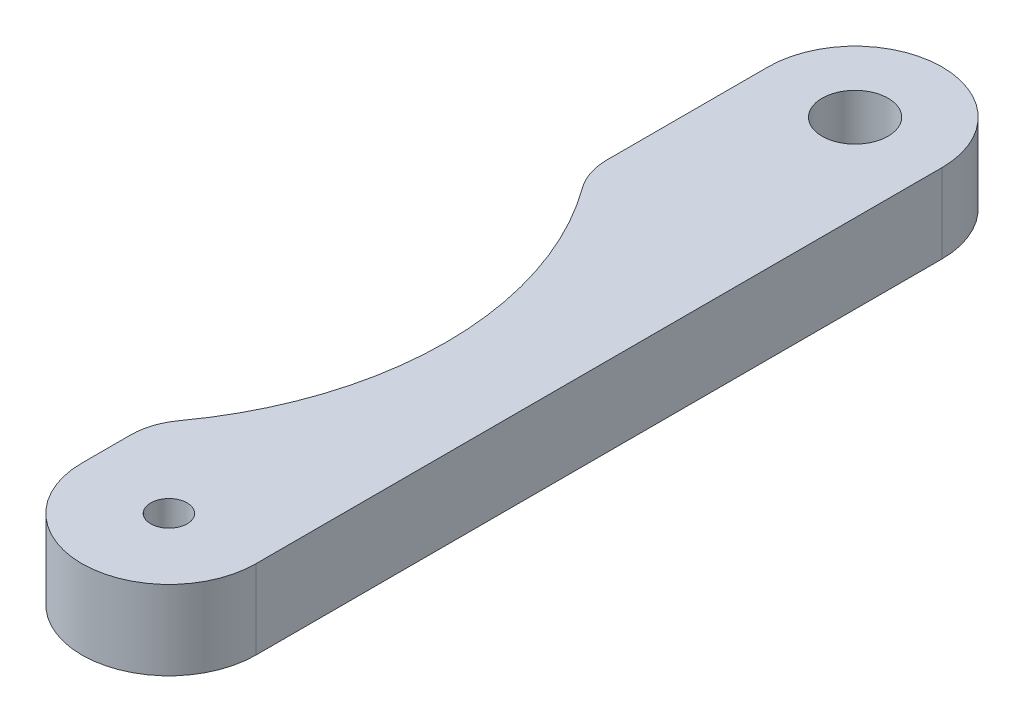
SolidWorks part; units mm, degrees
material "7075-T6, Plate (SS)"
ref_plane "Front Plane" through (0, 0, 0) normal (0, 0, 1) x (1, 0, 0)
ref_plane "Top Plane" through (0, 0, 0) normal (0, 1, 0) x (1, 0, 0)
ref_plane "Right Plane" through (0, 0, 0) normal (1, 0, 0) x (0, 0, -1)
sketch "Sketch1" plane through (0, 0, 0) normal (0, 1, 0) x (1, 0, 0)
  line L0 (0.3077, 6.5172) -> (0.3077, -26.5028)
  line L1 (8.6897, 6.5172) -> (8.6897, -26.5028)
  arc A0 (0.3077, 6.5172) -> (8.6897, 6.5172) centre (4.4987, 6.5172) cw
  arc A1 (8.6897, -26.5028) -> (0.3077, -26.5028) centre (4.4987, -26.5028) cw
  dimension "D1" = 33.02
  dimension "D2" = 8.382
extrude "Boss-Extrude1" add sketch "Sketch1" along normal blind 3.81
hole_wizard "#4-40 Tapped Hole1" positions "Sketch2" profile "Sketch3" tap size "#4-40" standard "ANSI Inch" end condition through all
sketch "Sketch2" plane through (0, 3.81, 0) normal (0, 1, 0) x (1, 0, 0)
  arc A0 (0.3077, -26.5028) -> (8.6897, -26.5028) centre (4.4987, -26.5028) ccw construction
  arc A1 (8.6897, 6.5172) -> (0.3077, 6.5172) centre (4.4987, 6.5172) ccw construction
  point P0 (4.4987, 6.5172)
  point P2 (4.4987, -26.5028)
sketch "Sketch3" plane through (4.4987, 3.81, -6.5172) normal (1, 0, 0) x (0, 0, 1)
  line L0 (0, 0) -> (0, 3.81)
  line L1 (0, 3.81) -> (0.8763, 3.81)
  line L2 (0.8763, 3.81) -> (0.8763, 0)
  line L5 (0.8763, 0) -> (0, 0)
  line L11 (0, -6.35) -> (0, 107.95) construction
  dimension "Thru Tap Drill Dia." = 1.7526
  dimension "Thru Tap Drill Depth" = 3.81
cosmetic thread "Hole Thread1" parameters "D2"=2.8448
cosmetic thread "Hole Thread2" parameters "D2"=2.8448
sketch "Sketch4" plane through (0, 3.81, 0) normal (0, 1, 0) x (1, 0, 0)
  line L0 (0.3077, -17.1048) -> (-18.1923, -17.1048) construction
  line L1 (0.3077, 6.5172) -> (0.3077, -26.5028) construction
  circle A1 centre (4.4987, -26.5028) radius 0.8763 construction
  arc A5 (-22.8682, -25.473) -> (-2.034, 0.0929) centre (-12.4511, -12.69) ccw
  dimension "D1" = 16.49
  dimension "D2" = 9.398
  dimension "D3" = 18.5
extrude "Cut-Extrude1" cut sketch "Sketch4" against normal through all
sketch "Sketch5" plane through (0, 3.81, 0) normal (0, 1, 0) x (1, 0, 0)
  circle A0 centre (4.4987, 6.5172) radius 1.5875
extrude "Cut-Extrude2" cut sketch "Sketch5" against normal through all
fillet "Fillet1" radius 3 2 edges at (0.3077, 1.905, 23.1367) (0.3077, 1.905, 2.2433)
